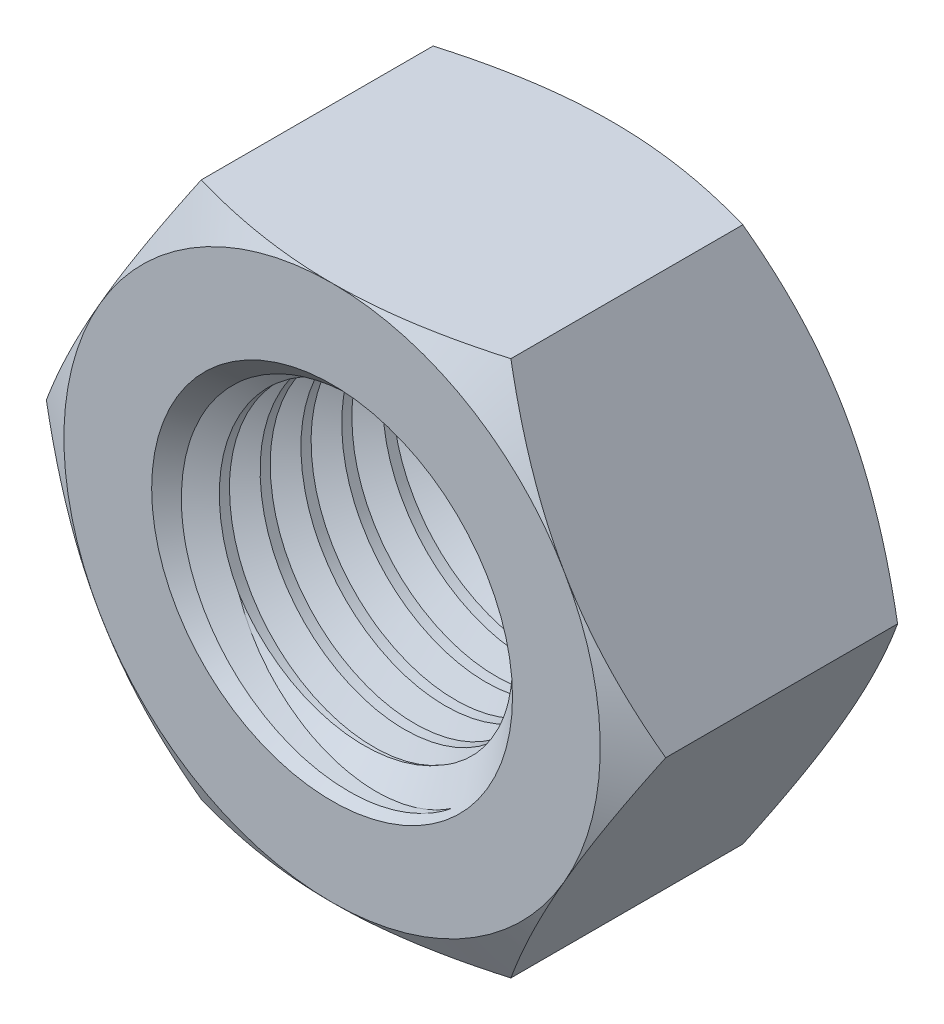
SolidWorks part; units mm, degrees
ref_plane "Front" through (0, 0, 0) normal (0, 0, 1) x (1, 0, 0)
ref_plane "Top" through (0, 0, 0) normal (0, 1, 0) x (1, 0, 0)
ref_plane "Right" through (0, 0, 0) normal (1, 0, 0) x (0, 0, -1)
sketch "Çizim1" plane through (0, 0, 0) normal (0, 0, 1) x (1, 0, 0)
  line L1 (26.5581, 0) -> (13.2791, 23)
  line L2 (13.2791, 23) -> (-13.2791, 23)
  line L3 (-13.2791, 23) -> (-26.5581, 0)
  line L4 (-26.5581, 0) -> (-13.2791, -23)
  line L5 (-13.2791, -23) -> (13.2791, -23)
  line L6 (13.2791, -23) -> (26.5581, 0)
  circle A0 centre (0, 0) radius 23 construction
  point P1 (0, 0)
  dimension "D1" = 46
extrude "Yükseklik-Ekstrüzyon1" add sketch "Çizim1" along normal blind 24
sketch "Çizim2" plane through (0, 0, 24) normal (0, 0, 1) x (1, 0, 0)
  circle A0 centre (0, 0) radius 23
extrude "Kes-Ekstrüzyon1" cut sketch "Çizim2" against normal blind 24 draft 60 flip side to cut
sketch "Çizim3" plane through (0, 0, 0) normal (0, 0, -1) x (-1, 0, 0)
  circle A0 centre (0, 0) radius 23
extrude "Kes-Ekstrüzyon2" cut sketch "Çizim3" against normal blind 24 draft 60 flip side to cut
sketch "Çizim4" plane through (0, 0, 0) normal (0, 0, -1) x (-1, 0, 0)
  circle A0 centre (0, 0) radius 12.725
  dimension "D1" = 25.45
extrude "Kes-Ekstrüzyon3" cut sketch "Çizim4" against normal blind 24
chamfer "Pah1" distance 2.75 angle 45 2 edges at (-12.725, 0, 24) (-12.725, 0, 0)
sketch "Çizim5" plane through (0, 0, 24) normal (0, 0, 1) x (1, 0, 0)
  circle A0 centre (0, 0) radius 12.725
curve "Helis/Spiral1" pitch 3.5 height 27 radius 12.725 centre (0, 0, 24) axis (0, 0, -1) start towards (1, 0, 0)
ref_plane "Düzlem1" through (-2.8316, 12.406, -3) normal (0.974, 0.2223, -0.0437) x (-0.0426, -0.0097, -0.999)
sketch "Çizim6" plane through (-2.8316, 12.406, -3) normal (0.974, 0.2223, -0.0437) x (-0.0426, -0.0097, -0.999)
  line L0 (-1.6583, -0.5973) -> (1.6583, -0.5973)
  line L1 (0, 2.275) -> (-1.6583, -0.5973)
  line L3 (1.6583, -0.5973) -> (0, 2.275)
  line L5 (-1.9702, -1.1375) -> (0, -1.1375) [skipped]
  circle A0 centre (0, 0) radius 1.1375 construction
  dimension "D1" = 2.275
sweep "Kes-Süpür1" cut profiles "Çizim6" path "Helis/Spiral1" align with end faces yes
